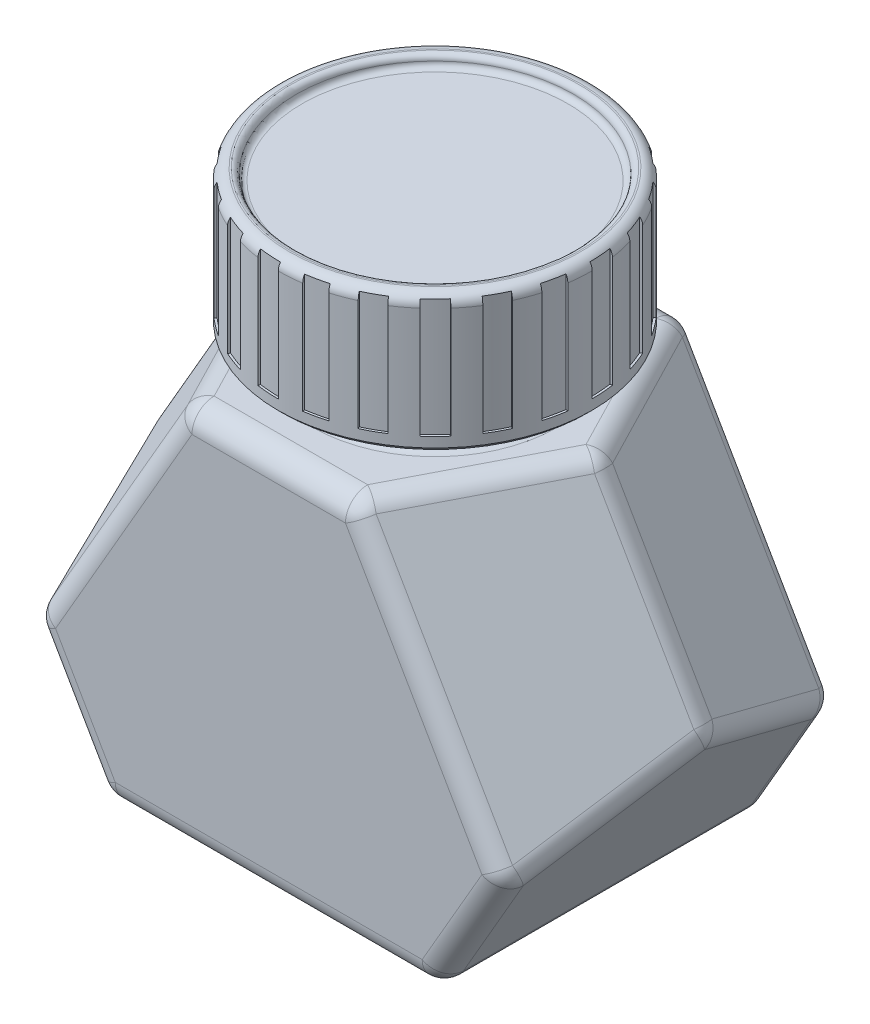
SolidWorks part; units mm, degrees
material "ABS"
ref_plane "Front Plane" through (0, 0, 0) normal (0, 0, 1) x (1, 0, 0)
ref_plane "Top Plane" through (0, 0, 0) normal (0, 1, 0) x (1, 0, 0)
ref_plane "Right Plane" through (0, 0, 0) normal (1, 0, 0) x (0, 0, -1)
sketch "Sketch2" plane through (0, 0, 0) normal (0, 0, 1) x (1, 0, 0)
  line L0 (50.8, 0) -> (12.7, 0)
  line L1 (0, 0) -> (63.5, 0) construction
  line L2 (0, 0) -> (0, 43.9941) construction
  line L3 (0, 43.9941) -> (63.5, 43.9941) construction
  line L4 (63.5, 0) -> (63.5, 43.9941) construction
  line L5 (12.7, 0) -> (0, 21.997)
  line L6 (0, 21.997) -> (12.7, 43.9941)
  line L7 (12.7, 43.9941) -> (12.7, 0) construction
  line L8 (31.75, 0) -> (31.75, 43.9941) construction
  line L9 (50.8, 0) -> (63.5, 21.997)
  line L10 (63.5, 21.997) -> (50.8, 43.9941)
  line L11 (12.7, 43.9941) -> (50.8, 43.9941)
  line L12 (0, 21.997) -> (9.9498, 21.997) construction
  dimension "D1" = 63.5
  dimension "D2" = 60
  dimension "D3" = 19.05
extrude "Boss-Extrude1" add sketch "Sketch2" along normal blind 38.1
sketch "Sketch3" plane through (0, 0, 0) normal (0, 0, 1) x (1, 0, 0)
  line L0 (12.7, 43.9941) -> (35.6529, 57.2459) construction
  line L1 (50.8, 43.9941) -> (12.7, 43.9941) construction
  line L2 (50.8, 43.9941) -> (50.8, 29.9162) construction
  line L3 (63.5, 21.997) -> (50.8, 43.9941) construction
  dimension "D1" = 30
  dimension "D2" = 30
ref_plane "Plane1" through (0, 0, 38.1) normal (0, 0, 1) x (1, 0, 0)
sketch "Sketch4" plane through (0, 0, 38.1) normal (0, 0, 1) x (1, 0, 0)
  line L0 (12.7, 43.9941) -> (35.6529, 57.2459) construction
  line L1 (12.7, 43.9941) -> (35.6529, 57.2459) construction
ref_plane "Plane2" through (-15.875, 27.4963, 0) normal (-0.5, 0.866, 0) x (0.866, 0.5, 0)
sketch "Sketch5" plane through (-15.875, 27.4963, 0) normal (-0.5, 0.866, 0) x (0.866, 0.5, 0)
  line L0 (57.4867, 0) -> (65.9911, -19.05)
  line L3 (65.9911, 0) -> (32.9956, 0) construction
  line L5 (65.9911, -38.1) -> (65.9911, 0) construction
  line L6 (65.9911, -19.05) -> (57.4867, -38.1)
  line L7 (65.9911, -38.1) -> (32.9956, -38.1) construction
  line L8 (57.4867, -38.1) -> (69.7532, -41.6974)
  line L9 (69.7532, -41.6974) -> (70.2941, 8.6765)
  line L10 (70.2941, 8.6765) -> (57.4867, 0)
  line L11 (57.4867, 0) -> (57.4867, -38.1) construction
extrude "Cut-Extrude1" cut sketch "Sketch5" against normal through all
ref_plane "Plane3" through (31.75, 0, 0) normal (1, 0, 0) x (0, 0, -1)
mirror "Mirror1" about plane through (31.75, 0, 0) normal (1, 0, 0) of "Cut-Extrude1"
sketch "Sketch6" plane through (0, 43.9941, 0) normal (0, 1, 0) x (1, 0, 0)
  line L0 (22.52, 0) -> (40.98, -38.1) construction
  circle A0 centre (31.75, -19.05) radius 12.7
  dimension "D1" = 25.4
extrude "Boss-Extrude2" add sketch "Sketch6" along normal blind 3.175
fillet "Fillet1" radius 2.54 24 edges at (31.75, 43.9941, 0) (8.805, 6.7463, 0) (13.715, 28.7434, 0) (17.61, 43.9941, 9.525) (2.455, 17.7448, 9.525) (6.35, 32.9956, 19.05) (17.61, 43.9941, 28.575) (2.455, 17.7448, 28.575) (12.7, 0, 19.05) (31.75, 0, 0) (45.89, 43.9941, 9.525) (49.785, 28.7434, 0) (54.695, 6.7463, 0) (50.8, 0, 19.05) (61.045, 17.7448, 9.525) (61.045, 17.7448, 28.575) (45.89, 43.9941, 28.575) (57.15, 32.9956, 19.05) (31.75, 43.9941, 38.1) (49.785, 28.7434, 38.1) (54.695, 6.7463, 38.1) (31.75, 0, 38.1) (8.805, 6.7463, 38.1) (13.715, 28.7434, 38.1)
fillet "Fillet2" radius 1.27 1 edges at (31.75, 43.9941, 6.35)
sketch "Sketch7" plane through (0, 47.1691, 0) normal (0, 1, 0) x (1, 0, 0)
  circle A0 centre (31.75, -19.05) radius 17.9578
  dimension "D1" = 35.9156
extrude "Boss-Extrude3" add sketch "Sketch7" along normal blind 15.621
sketch "Sketch8" plane through (0, 62.7901, 0) normal (0, 1, 0) x (1, 0, 0)
  line L0 (31.75, -19.05) -> (31.75, -1.0922) construction
  line L1 (31.75, -1.0922) -> (31.75, -1.3462)
  line L2 (31.75, -19.05) -> (34.2492, -1.267) construction
  line L3 (34.2139, -1.5185) -> (34.2492, -1.267)
  line L4 (36.8093, -1.8196) -> (36.7377, -2.0633)
  line L5 (39.0533, -2.9228) -> (39.1581, -2.6914)
  line L6 (41.4587, -3.9429) -> (41.3214, -4.1566)
  line L7 (43.301, -5.6336) -> (43.4667, -5.4412)
  line L8 (45.3216, -7.2901) -> (45.1296, -7.4565)
  line L9 (46.6129, -9.4314) -> (46.8262, -9.2934)
  line L10 (48.085, -11.5901) -> (47.8539, -11.6956)
  line L11 (48.7208, -14.0084) -> (48.9642, -13.9361)
  line L12 (49.525, -16.4943) -> (49.2736, -16.5305)
  line L13 (49.4537, -18.9938) -> (49.7077, -18.993)
  line L14 (49.525, -21.6057) -> (49.2736, -21.5695)
  line L15 (48.7524, -23.9838) -> (48.9964, -24.0546)
  line L16 (48.085, -26.5099) -> (47.8539, -26.4044)
  line L17 (46.6737, -28.5741) -> (46.8878, -28.7107)
  line L18 (45.3216, -30.8099) -> (45.1296, -30.6435)
  line L19 (43.3859, -32.3928) -> (43.5529, -32.5842)
  line L20 (41.4587, -34.1571) -> (41.3214, -33.9434)
  line L21 (39.1555, -35.1305) -> (39.2617, -35.3612)
  line L22 (36.8093, -36.2804) -> (36.7377, -36.0367)
  line L23 (34.3251, -36.5655) -> (34.3621, -36.8168)
  line L24 (31.75, -37.0078) -> (31.75, -36.7538)
  line L25 (29.2861, -36.5815) -> (29.2508, -36.833)
  line L26 (26.6907, -36.2804) -> (26.7623, -36.0367)
  line L27 (24.4467, -35.1772) -> (24.3419, -35.4086)
  line L28 (22.0413, -34.1571) -> (22.1786, -33.9434)
  line L29 (20.199, -32.4664) -> (20.0333, -32.6588)
  line L30 (18.1784, -30.8099) -> (18.3704, -30.6435)
  line L31 (16.8871, -28.6686) -> (16.6738, -28.8066)
  line L32 (15.415, -26.5099) -> (15.6461, -26.4044)
  line L33 (14.7792, -24.0916) -> (14.5358, -24.1639)
  line L34 (13.975, -21.6057) -> (14.2264, -21.5695)
  line L35 (14.0463, -19.1062) -> (13.7923, -19.107)
  line L36 (13.975, -16.4943) -> (14.2264, -16.5305)
  line L37 (14.7476, -14.1162) -> (14.5036, -14.0454)
  line L38 (15.415, -11.5901) -> (15.6461, -11.6956)
  line L39 (16.8263, -9.5259) -> (16.6122, -9.3893)
  line L40 (18.1784, -7.2901) -> (18.3704, -7.4565)
  line L41 (20.1141, -5.7072) -> (19.9471, -5.5158)
  line L42 (22.0413, -3.9429) -> (22.1786, -4.1566)
  line L43 (24.3445, -2.9695) -> (24.2383, -2.7388)
  line L44 (26.6907, -1.8196) -> (26.7623, -2.0633)
  line L45 (29.1749, -1.5345) -> (29.1379, -1.2832)
  circle A0 centre (31.75, -19.05) radius 17.9578 construction
  arc A1 (34.2139, -1.5185) -> (31.75, -1.3462) centre (31.75, -19.05) ccw
  arc A3 (34.2492, -1.267) -> (31.75, -1.0922) centre (31.75, -19.05) ccw
  arc A4 (39.1581, -2.6914) -> (36.8093, -1.8196) centre (31.75, -19.05) ccw
  arc A5 (39.0533, -2.9228) -> (36.7377, -2.0633) centre (31.75, -19.05) ccw
  arc A6 (43.4667, -5.4412) -> (41.4587, -3.9429) centre (31.75, -19.05) ccw
  arc A7 (43.301, -5.6336) -> (41.3214, -4.1566) centre (31.75, -19.05) ccw
  arc A8 (46.8262, -9.2934) -> (45.3216, -7.2901) centre (31.75, -19.05) ccw
  arc A9 (46.6129, -9.4314) -> (45.1296, -7.4565) centre (31.75, -19.05) ccw
  arc A10 (48.9642, -13.9361) -> (48.085, -11.5901) centre (31.75, -19.05) ccw
  arc A11 (48.7208, -14.0084) -> (47.8539, -11.6956) centre (31.75, -19.05) ccw
  arc A12 (49.7077, -18.993) -> (49.525, -16.4943) centre (31.75, -19.05) ccw
  arc A13 (49.4537, -18.9938) -> (49.2736, -16.5305) centre (31.75, -19.05) ccw
  arc A14 (48.9964, -24.0546) -> (49.525, -21.6057) centre (31.75, -19.05) ccw
  arc A15 (48.7524, -23.9838) -> (49.2736, -21.5695) centre (31.75, -19.05) ccw
  arc A16 (46.8878, -28.7107) -> (48.085, -26.5099) centre (31.75, -19.05) ccw
  arc A17 (46.6737, -28.5741) -> (47.8539, -26.4044) centre (31.75, -19.05) ccw
  arc A18 (43.5529, -32.5842) -> (45.3216, -30.8099) centre (31.75, -19.05) ccw
  arc A19 (43.3859, -32.3928) -> (45.1296, -30.6435) centre (31.75, -19.05) ccw
  arc A20 (39.2617, -35.3612) -> (41.4587, -34.1571) centre (31.75, -19.05) ccw
  arc A21 (39.1555, -35.1305) -> (41.3214, -33.9434) centre (31.75, -19.05) ccw
  arc A22 (34.3621, -36.8168) -> (36.8093, -36.2804) centre (31.75, -19.05) ccw
  arc A23 (34.3251, -36.5655) -> (36.7377, -36.0367) centre (31.75, -19.05) ccw
  arc A24 (29.2508, -36.833) -> (31.75, -37.0078) centre (31.75, -19.05) ccw
  arc A25 (29.2861, -36.5815) -> (31.75, -36.7538) centre (31.75, -19.05) ccw
  arc A26 (24.3419, -35.4086) -> (26.6907, -36.2804) centre (31.75, -19.05) ccw
  arc A27 (24.4467, -35.1772) -> (26.7623, -36.0367) centre (31.75, -19.05) ccw
  arc A28 (20.0333, -32.6588) -> (22.0413, -34.1571) centre (31.75, -19.05) ccw
  arc A29 (20.199, -32.4664) -> (22.1786, -33.9434) centre (31.75, -19.05) ccw
  arc A30 (16.6738, -28.8066) -> (18.1784, -30.8099) centre (31.75, -19.05) ccw
  arc A31 (16.8871, -28.6686) -> (18.3704, -30.6435) centre (31.75, -19.05) ccw
  arc A32 (14.5358, -24.1639) -> (15.415, -26.5099) centre (31.75, -19.05) ccw
  arc A33 (14.7792, -24.0916) -> (15.6461, -26.4044) centre (31.75, -19.05) ccw
  arc A34 (13.7923, -19.107) -> (13.975, -21.6057) centre (31.75, -19.05) ccw
  arc A35 (14.0463, -19.1062) -> (14.2264, -21.5695) centre (31.75, -19.05) ccw
  arc A36 (14.5036, -14.0454) -> (13.975, -16.4943) centre (31.75, -19.05) ccw
  arc A37 (14.7476, -14.1162) -> (14.2264, -16.5305) centre (31.75, -19.05) ccw
  arc A38 (16.6122, -9.3893) -> (15.415, -11.5901) centre (31.75, -19.05) ccw
  arc A39 (16.8263, -9.5259) -> (15.6461, -11.6956) centre (31.75, -19.05) ccw
  arc A40 (19.9471, -5.5158) -> (18.1784, -7.2901) centre (31.75, -19.05) ccw
  arc A41 (20.1141, -5.7072) -> (18.3704, -7.4565) centre (31.75, -19.05) ccw
  arc A42 (24.2383, -2.7388) -> (22.0413, -3.9429) centre (31.75, -19.05) ccw
  arc A43 (24.3445, -2.9695) -> (22.1786, -4.1566) centre (31.75, -19.05) ccw
  arc A44 (29.1379, -1.2832) -> (26.6907, -1.8196) centre (31.75, -19.05) ccw
  arc A45 (29.1749, -1.5345) -> (26.7623, -2.0633) centre (31.75, -19.05) ccw
  point P94 (31.75, -19.05)
  dimension "D1" = 0.254
  dimension "D2" = 8
  dimension "D3" = 22
extrude "Cut-Extrude2" cut sketch "Sketch8" against normal blind 13.97
sketch "Sketch9" plane through (0, 62.7901, 0) normal (0, 1, 0) x (1, 0, 0)
  circle A0 centre (31.75, -19.05) radius 15.875
  dimension "D1" = 31.75
extrude "Cut-Extrude3" cut sketch "Sketch9" against normal blind 1.27
fillet "Fillet4" radius 0.635 2 edges at (31.75, 61.5201, 34.925) (31.75, 62.7901, 34.925)
sketch "Sketch10" plane through (31.75, 0, 0) normal (1, 0, 0) x (0, 0, -1)
  line L0 (-1.0922, 62.7901) -> (-2.3622, 62.7901) construction
  line L1 (-5.4412, 62.7901) -> (-7.2901, 62.7901) construction
  line L2 (-1.0922, 62.7901) -> (-1.0922, 61.5201) construction
  line L3 (-1.0922, 48.8201) -> (-1.0922, 62.7901) construction
  line L4 (-2.3622, 62.7901) -> (-2.3622, 61.5201) construction
  line L5 (-2.3622, 61.5201) -> (-1.0922, 61.5201) construction
  line L6 (-2.3622, 62.7901) -> (-2.3622, 63.7949)
  line L7 (-2.3622, 63.7949) -> (-1.0922, 65.9614)
  line L8 (-1.0922, 65.9614) -> (2.7669, 64.4638)
  line L9 (2.7669, 64.4638) -> (1.3154, 61.7723)
  line L10 (1.3154, 61.7723) -> (-1.0922, 61.5201)
  line L11 (-19.05, 0) -> (-19.05, -50000) construction
  line L12 (-2.54, 0) -> (-35.56, 0) construction
  arc A0 (-1.0922, 61.5201) -> (-2.3622, 62.7901) centre (-2.3622, 61.5201) ccw
  point P17 (-19.05, 0)
  dimension "D1" = 1.27
revolve "Cut-Revolve2" cut sketch "Sketch10" angle 360 about L11
chamfer "Chamfer1" distance 0.508 angle 45 1 edges at (31.75, 47.1691, 37.0078)
